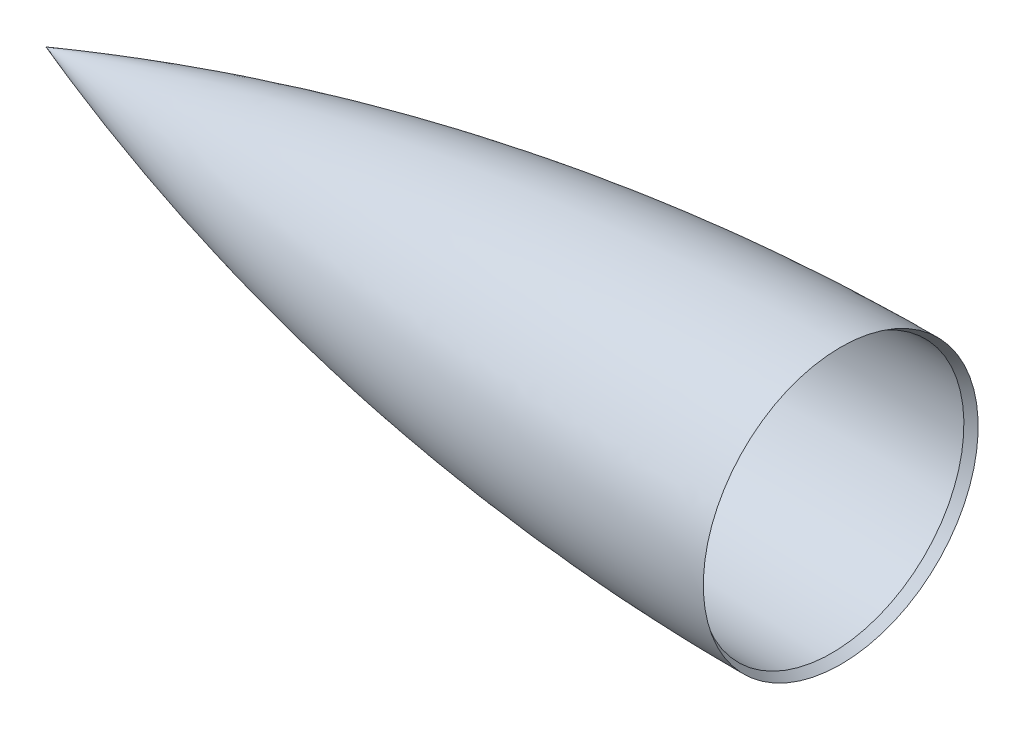
SolidWorks part; units mm, degrees
ref_plane "Front Plane" through (0, 0, 0) normal (0, 0, 1) x (1, 0, 0)
ref_plane "Top Plane" through (0, 0, 0) normal (0, 1, 0) x (1, 0, 0)
ref_plane "Right Plane" through (0, 0, 0) normal (1, 0, 0) x (0, 0, -1)
sketch "Sketch1" plane through (0, 0, 0) normal (0, 0, 1) x (1, 0, 0)
  line L0 (0, 0) -> (-229, 0) construction
  line L1 (0, 36.6) -> (0, -642.3338) construction
  line L3 (-229, 0) -> (-219.9054, 0)
  line L4 (83, 38.1) -> (2.5981, 38.1)
  line L7 (0, 39.6) -> (83, 39.6)
  line L8 (83, 38.1) -> (83, 39.6)
  line L9 (0, 36.6) -> (2.5981, 38.1)
  line L10 (0, 36.6) -> (119.7357, 36.6) construction
  line L11 (2.5981, 38.1) -> (119.7357, 38.1) construction
  line L12 (119.7357, 36.6) -> (119.7357, 38.1) construction
  line L13 (-79.2, 81.783) -> (-79.2, 33.475) construction
  line L15 (0, 39.6) -> (-2.6067, 38.095)
  line L16 (-79.2, 33.475) -> (-82.5018, 31.5687)
  line L17 (-79.2, 31.9647) -> (-79.2, -62.4632) construction
  circle A0 centre (0, -642.3338) radius 681.9338 construction
  arc A1 (-229, 0) -> (0, 39.6) centre (0, -642.3338) cw
  arc A2 (-219.9054, 0) -> (0, 36.6) centre (0, -642.3338) cw
  arc A3 (-227.9926, -2.8258) -> (0, 36.6) centre (0, -642.3338) cw construction
  arc A4 (-79.2, 33.475) -> (-2.6067, 38.095) centre (0, -642.3338) cw
  arc A5 (-220.3913, 1.4191) -> (0, 38.1) centre (0, -642.3338) cw construction
  point P0 (0, 39.6)
  dimension "D1" = 39.6
  dimension "D2" = 229
  dimension "D3" = 681.9338
  dimension "D5" = 83
  dimension "D6" = 1.5
  dimension "D7" = 30
  dimension "D8" = 80.4019
  dimension "D9" = 1.5
  dimension "D10" = 38.1
  dimension "D11" = 1.5
  dimension "D12" = 79.2
  dimension "D13" = 30
  dimension "D14" = 30
  dimension "D4" = 3
revolve "Revolve1" add sketch "Sketch1" angle 360 about L0 region at (-115.8034, 27.3371, 0)
